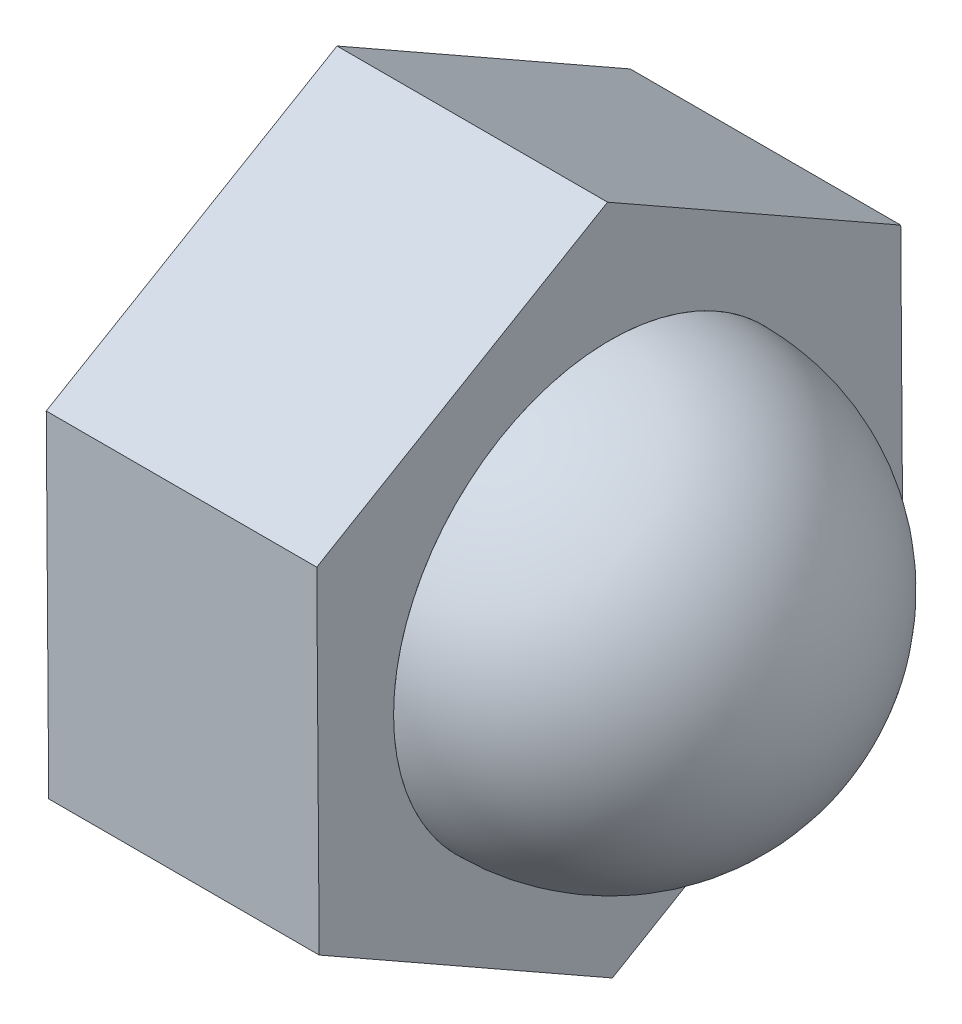
SolidWorks part; units mm, degrees
ref_plane "Front Plane" through (0, 0, 0) normal (0, 0, 1) x (1, 0, 0)
ref_plane "Top Plane" through (0, 0, 0) normal (0, 1, 0) x (1, 0, 0)
ref_plane "Right Plane" through (0, 0, 0) normal (1, 0, 0) x (0, 0, -1)
sketch "Sketch1" plane through (1066.9457, 0, 0) normal (1, 0, 0) x (0, 0, -1)
  line L1 (-1242.405, 968.7214) -> (-1242.5408, 987.4176)
  line L2 (-1242.5408, 987.4176) -> (-1258.8, 996.6481)
  line L3 (-1258.8, 996.6481) -> (-1274.9235, 987.1824)
  line L4 (-1274.9235, 987.1824) -> (-1274.7877, 968.4862)
  line L5 (-1274.7877, 968.4862) -> (-1258.5284, 959.2557)
  line L6 (-1258.5284, 959.2557) -> (-1242.405, 968.7214)
  circle A0 centre (-1258.6642, 977.9519) radius 12 construction
  circle A1 centre (-1258.6642, 977.9519) radius 12
  circle A2 centre (-1258.6642, 977.9519) radius 16.1918 construction
extrude "Boss-Extrude1" add sketch "Sketch1" against normal blind 15
sketch "Sketch2" plane through (1066.9457, 0, 0) normal (1, 0, 0) x (0, 0, -1)
  line L0 (-1258.6642, 989.9519) -> (-1258.6642, 965.9519)
  circle A0 centre (-1258.6642, 977.9519) radius 12 construction
  circle A1 centre (-1258.6642, 977.9519) radius 12 construction
  arc A2 (-1258.6642, 965.9519) -> (-1258.6642, 989.9519) centre (-1258.6642, 977.9519) ccw
revolve "Revolve1" add sketch "Sketch2" angle 180 about L0
thread "Thread1" pitch 2 method cut profile "Thread Profile1" start angle 0, offset 0, length 13, pitch 2, diameter 24
ref_plane "Plane1" through (1051.9457, 977.9519, 1246.6642) normal (0, -1, 0) x (0, 0, -1)
sketch "Thread Profile1" plane through (1051.9457, 977.9519, 1246.6642) normal (0, -1, 0) x (0, 0, -1)
  line L0 (0, 0) -> (0, 2) construction
  line L1 (0, 0) -> (1.0825, 0.625)
  line L2 (1.0825, 0.625) -> (1.0825, 0.875)
  line L3 (1.0825, 0.875) -> (0, 1.5)
  line L4 (1.0825, 0.75) -> (0, 0.75) construction
  line L11 (0, 0) -> (0, 1.5)
  point P2 (0, 0)
  dimension "Pitch" = 2
  dimension "Profile_Angle" = 60
  dimension "Profile_Land" = 0.25
  dimension "Profile_Height" = 1.0825
